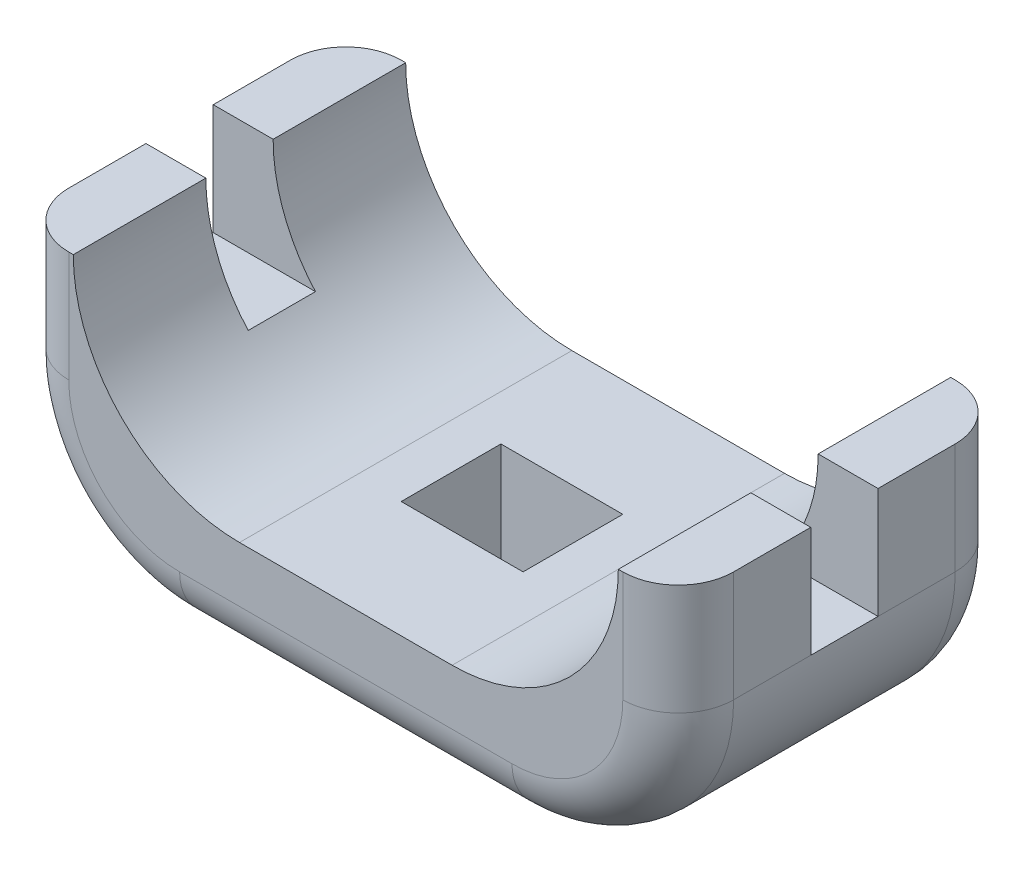
SolidWorks part; units mm, degrees
material "PET"
ref_plane "Спереди" through (0, 0, 0) normal (0, 0, 1) x (1, 0, 0)
ref_plane "Сверху" through (0, 0, 0) normal (0, 1, 0) x (1, 0, 0)
ref_plane "Справа" through (0, 0, 0) normal (1, 0, 0) x (0, 0, -1)
other "Configuration Table"
sketch "Эскиз1" plane through (0, 0, 0) normal (0, 1, 0) x (1, 0, 0)
  line L1 (6, -3) -> (-6, -3)
  line L2 (6, -3) -> (6, 3)
  line L3 (6, 3) -> (-6, 3)
  line L4 (-6, -3) -> (-6, 3)
  line L5 (0, 3) -> (0, -3) construction
  line L6 (6, 0) -> (-6, 0) construction
  point P0 (0, 0)
  dimension "D1" = 12
  dimension "D2" = 6
extrude "Бобышка-Вытянуть1" add sketch "Эскиз1" along normal blind 5
sketch "Эскиз2" plane through (0, 0, 0) normal (0, -1, 0) x (1, 0, 0)
  line L1 (-1.1, -0.9) -> (1.1, -0.9)
  line L2 (-1.1, -0.9) -> (-1.1, 0.9)
  line L3 (-1.1, 0.9) -> (1.1, 0.9)
  line L4 (1.1, -0.9) -> (1.1, 0.9)
  line L5 (0, 0.9) -> (0, -0.9) construction
  line L6 (-1.1, 0) -> (1.1, 0) construction
  point P1 (0, 0)
  dimension "D1" = 1.8
  dimension "D2" = 2.2
extrude "Вырез-Вытянуть1" cut sketch "Эскиз2" against normal blind 5
fillet "Скругление1" radius 3 2 edges at (6, 0, 0) (-6, 0, 0)
sketch "Эскиз3" plane through (0, 5, 0) normal (0, 1, 0) x (1, 0, 0)
  line L0 (0, 3) -> (0, -3) construction
  line L1 (6, 3) -> (-6, 3) construction
  line L2 (-6, -3) -> (6, -3) construction
  line L3 (-6, 0) -> (6, 0) construction
  line L4 (-6, 3) -> (-6, -3) construction
  line L5 (6, -3) -> (6, 3) construction
  line L7 (-4.919, -3) -> (4.919, -3)
  line L8 (-4.919, -3) -> (-4.919, 3)
  line L9 (-4.919, 3) -> (4.919, 3)
  line L10 (4.919, -3) -> (4.919, 3)
  line L11 (0, 3) -> (0, -3) construction
  line L12 (-4.919, 0) -> (4.919, 0) construction
  point P12 (0, 0)
extrude "Вырез-Вытянуть2" cut sketch "Эскиз3" against normal blind 3
fillet "Скругление2" radius 3 2 edges at (4.919, 2, 0) (-4.919, 2, 0)
fillet "Скругление3" radius 1 5 edges at (6, 4, -3) (5.1213, 0.8787, -3) (-6, 4, -3) (-5.1213, 0.8787, -3) (0, 0, -3)
fillet "Скругление4" radius 1 5 edges at (-6, 4, 3) (-5.1213, 0.8787, 3) (0, 0, 3) (6, 4, 3) (5.1213, 0.8787, 3)
sketch "Эскиз4" plane through (0, 5, 0) normal (0, 1, 0) x (1, 0, 0)
  line L0 (-6, 0) -> (6, 0) construction
  line L1 (-6, 2) -> (-6, -2) construction
  line L2 (6, -2) -> (6, 2) construction
  line L4 (-6, -0.6073) -> (6, -0.6073)
  line L5 (-6, -0.6073) -> (-6, 0.6073)
  line L6 (-6, 0.6073) -> (6, 0.6073)
  line L7 (6, -0.6073) -> (6, 0.6073)
  line L8 (0, 0.6073) -> (0, -0.6073) construction
  line L9 (-6, 0) -> (6, 0) construction
  point P6 (0, 0)
extrude "Вырез-Вытянуть3" cut sketch "Эскиз4" against normal blind 2
